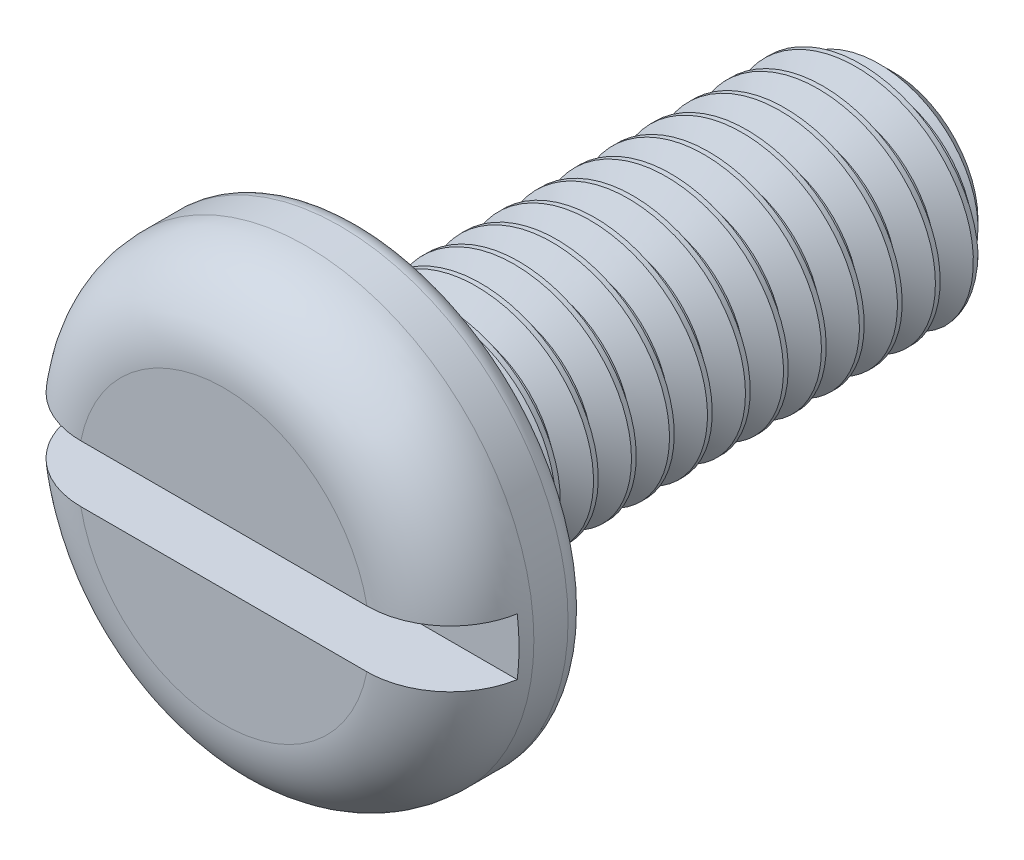
SolidWorks part; units mm, degrees
ref_plane "Front" through (0, 0, 0) normal (0, 0, 1) x (1, 0, 0)
ref_plane "Top" through (0, 0, 0) normal (0, 1, 0) x (1, 0, 0)
ref_plane "Right" through (0, 0, 0) normal (1, 0, 0) x (0, 0, -1)
sketch "Sketch1" plane through (0, 0, 0) normal (0, 0, 1) x (1, 0, 0)
  circle A0 centre (0, 0) radius 6
  dimension "Head Dia" = 12
extrude "Extrude3" add sketch "Sketch1" along normal blind 3.6
sketch "Sketch11" plane through (0, 0, 0) normal (1, 0, 0) x (0, 0, -1)
  line L0 (0.4414, 0) -> (-3.6, 0) construction
  line L1 (-3.6, 3.84) -> (-3.8, 3.84)
  line L2 (-3.8, 3.84) -> (-3.8, 6.2)
  line L3 (0, -6) -> (0, 6) construction
  line L4 (-3.8, 6.2) -> (0, 6.2)
  line L5 (-1.44, 6) -> (0, 6)
  line L6 (-3.6, 6) -> (-3.6, -6) construction
  line L7 (0, 6) -> (0, 6.2)
  line L8 (0, 6) -> (-3.6, 6) construction
  line L9 (-3.6, 3.84) -> (-3.6, 0) construction
  arc A0 (-1.44, 6) -> (-3.6, 3.84) centre (-1.44, 3.84) ccw
  dimension "D2" = 2.16
  dimension "D1" = 0.2
  dimension "D3" = 3.6
revolve "Cut-Revolve3" cut sketch "Sketch11" angle 360 about L0
sketch "Sketch4" plane through (0, 0, 0) normal (1, 0, 0) x (0, 0, -1)
  line L0 (0, 0) -> (14, 0)
  line L2 (14, -3) -> (0, -3) construction
  line L3 (14, 0) -> (14, 3)
  line L4 (14, 3) -> (0, 3)
  line L6 (0, 3) -> (0, 0)
  line L7 (14, 0) -> (16.54, 0) construction
  dimension "D1" = 2.54
  dimension "Screw Dia" = 6
  dimension "Screw Length" = 14
revolve "Revolve1" add sketch "Sketch4" angle 360 about L7
chamfer "Chamfer1" distance 0.75 angle 45 1 edges at (3, 0, -14)
sketch "Sketch13" plane through (0, 0, 0) normal (1, 0, 0) x (0, 0, -1)
  line L0 (14, 3) -> (14.375, 2.3505)
  line L1 (14.375, 2.3505) -> (14.5, 2.3505)
  line L2 (14.5, 2.3505) -> (14.875, 3)
  line L3 (14.875, 3) -> (14, 3)
  line L4 (14.1875, 2.6752) -> (14.6875, 2.6752) construction
  dimension "D1" = 0.125
  dimension "D2" = 0.5
  dimension "D3" = 60
sketch "Sketch14" plane through (0, 0, -14) normal (0, 0, -1) x (-1, 0, 0)
  circle A1 centre (0, 0) radius 2.25
  circle A2 centre (0, 0) radius 2.25
  dimension "D1" = 0
curve "Helix/Spiral1" pitch 1 height 15 turns 15
sweep "Cut-Sweep1" cut profiles "Sketch13" path "Helix/Spiral1" align with end faces yes
sketch "Sketch12" plane through (0, 0, 3.6) normal (0, 0, 1) x (1, 0, 0)
  line L0 (6, -0.75) -> (6, 0.75)
  line L1 (6, 0) -> (-6, 0) construction
  line L2 (6, 0.75) -> (-6, 0.75)
  line L3 (-6, 0.75) -> (-6, -0.75)
  line L8 (-6, -0.75) -> (6, -0.75)
  circle A0 centre (0, 0) radius 6 construction
  dimension "Phillips Width" = 1.5
extrude "Cut-Extrude1" cut sketch "Sketch12" against normal blind 1.8
fillet "Fillet1" radius 0.54 1 edges at (6, 0, 0)
split line "Split Line1" [suppressed]
sketch "Sketch16" [suppressed] plane through (0, 0, 0) normal (1, 0, 0) x (0, 0, -1)
  point P0 (11.5, -3)
sketch "Sketch17" [suppressed] plane through (0, 0, -14) normal (0, 0, -1) x (-1, 0, 0)
  circle A0 centre (0, 0) radius 3
  point P3 (0, 3)
  point P5 (0, -3)
combine bodies "Combine1" [suppressed] operation type add bodies to combine 128 129
equation "\"D2@Sketch11\"=\"Head Ht@Extrude3\"*.6"
equation "\"D1@Cut-Extrude1\"=\"Head Ht@Extrude3\"*.5"
equation "\"Phillips Width@Sketch12\"=\"Head Dia@Sketch1\"/8"
equation "\"D2@Sketch13\" = \"D4@Helix/Spiral1\" * .5"
equation "\"D1@Sketch13\" = \"D4@Helix/Spiral1\" * .125"
equation "\"D1@Chamfer1\" = \"D4@Helix/Spiral1\" * .75"
equation "\"D3@Helix/Spiral1\" = \"Screw Length@Sketch4\" + \"D4@Helix/Spiral1\""
equation "\"D1@Fillet1\" = \"Head Ht@Extrude3\" * .15"
